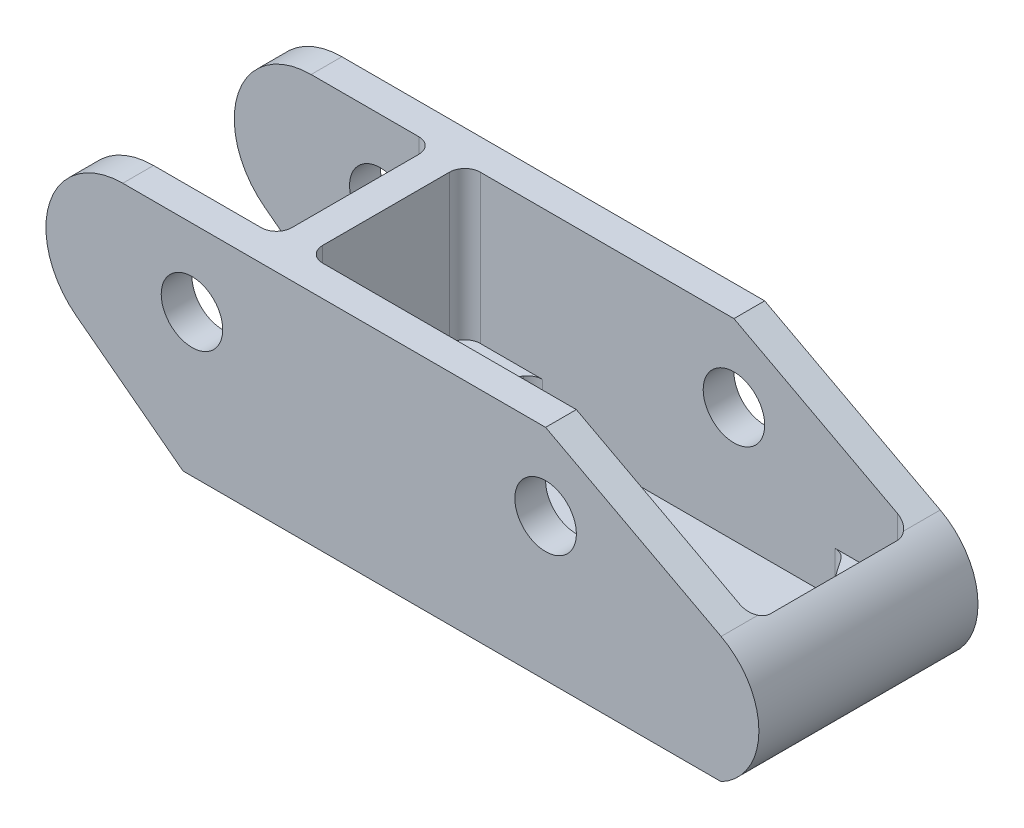
SolidWorks part; units mm, degrees
ref_plane "Front Plane" through (0, 0, 0) normal (0, 0, 1) x (1, 0, 0)
ref_plane "Top Plane" through (0, 0, 0) normal (0, 1, 0) x (1, 0, 0)
ref_plane "Right Plane" through (0, 0, 0) normal (1, 0, 0) x (0, 0, -1)
sketch "Sketch1" plane through (0, 0, 0) normal (0, 0, 1) x (1, 0, 0)
  line L0 (-35, 0) -> (35, 0)
  line L1 (-35, 0) -> (-48.879, 10.5347)
  line L2 (-42.833, 28.5) -> (12.167, 28.5)
  line L3 (12.167, 28.5) -> (35, 16.3595)
  line L4 (35, 0) -> (35, 45.6164) construction
  line L5 (12.167, 28.5) -> (12.167, -15.6419) construction
  arc A0 (-42.833, 28.5) -> (-48.879, 10.5347) centre (-42.833, 18.5) ccw
  arc A1 (35, 16.3595) -> (35, 0) centre (30.6508, 8.1797) cw
  circle A2 centre (12.167, 18.5) radius 4
  circle A4 centre (-33.833, 18.5) radius 4
  point P8 (0, 0)
  point P16 (0, 0)
  point P17 (0, 0)
  dimension "D4" = 10
  dimension "D8" = 8
  dimension "D1" = 142.8
  dimension "D2" = 28.5
  dimension "D3" = 70
  dimension "D5" = 55
  dimension "D6" = 152
  dimension "D7" = 10
  dimension "D9" = 46
extrude "Boss-Extrude1" add sketch "Sketch1" along normal mid plane 28.5
sketch "Sketch3" plane through (0, 28.5, 0) normal (0, 1, 0) x (1, 0, 0)
  line L0 (-52.833, 10.25) -> (-28.833, 10.25)
  line L1 (-52.833, 14.25) -> (-52.833, -14.25) construction
  line L2 (-26.833, 8.25) -> (-26.833, -8.25)
  line L3 (-28.833, -10.25) -> (-52.833, -10.25)
  line L4 (-52.833, -10.25) -> (-52.833, 10.25)
  line L5 (12.167, 14.25) -> (-42.833, 14.25) construction
  line L6 (12.167, -14.25) -> (-42.833, -14.25) construction
  line L7 (-20.833, 10.25) -> (33.4149, 10.25)
  line L8 (35.4149, 8.25) -> (35.4149, -8.25)
  line L9 (33.4149, -10.25) -> (-20.833, -10.25)
  line L10 (-22.833, -8.25) -> (-22.833, 8.25)
  line L11 (39.9149, -14.25) -> (39.9149, 14.25) construction
  arc A0 (35.4149, -8.25) -> (33.4149, -10.25) centre (33.4149, -8.25) cw
  arc A1 (33.4149, 10.25) -> (35.4149, 8.25) centre (33.4149, 8.25) cw
  arc A2 (-20.833, -10.25) -> (-22.833, -8.25) centre (-20.833, -8.25) cw
  arc A3 (-20.833, 10.25) -> (-22.833, 8.25) centre (-20.833, 8.25) ccw
  arc A4 (-26.833, -8.25) -> (-28.833, -10.25) centre (-28.833, -8.25) cw
  arc A5 (-28.833, 10.25) -> (-26.833, 8.25) centre (-28.833, 8.25) cw
  point P24 (-26.833, -10.25)
  point P27 (-26.833, 10.25)
  line M12 (-42.833, 14.25) -> (-42.833, -14.25)
  dimension "D5" = 2
  dimension "D1" = 4
  dimension "D2" = 4
  dimension "D3" = 26
  dimension "D4" = 4
  dimension "D6" = 4.5
extrude "Cut-Extrude1" cut sketch "Sketch3" against normal offset from surface (25 mm away) 3.5 contours A5 L0 L3 A4 L2 M12 | L4 L3 L0 M12 region at (-47.833, 28.5, 0) region at (-34.8727, 28.5, 0) up to face at (0, 0, 0)
extrude "Cut-Extrude2" cut sketch "Sketch3<3>" against normal blind 19.3 contours L9 A2 L10 A3 L7 A1 L8 A0
sketch "Sketch3<3>" plane through (0, 28.5, 0) normal (0, 1, 0) x (1, 0, 0) same geometry as "Sketch3"
sketch "Sketch6" plane through (0, 9.2, 0) normal (0, 1, 0) x (1, 0, 0)
  line L0 (-18.4833, 3.4067) -> (-14.3594, 9.3856)
  line L1 (-20.833, 10.25) -> (33.4149, 10.25) construction
  line L2 (-12.7131, 10.25) -> (25.295, 10.25)
  line L3 (26.9413, 9.3856) -> (31.0652, 3.4067)
  line L4 (31.0652, -3.4067) -> (26.9413, -9.3856)
  line L5 (33.4149, -10.25) -> (-20.833, -10.25) construction
  line L6 (25.295, -10.25) -> (-12.7131, -10.25)
  line L7 (-14.3594, -9.3856) -> (-18.4833, -3.4067)
  line L8 (-22.833, -8.25) -> (-22.833, 8.25) construction
  line L9 (35.4149, 8.25) -> (35.4149, -8.25) construction
  line L10 (35.4149, 8.25) -> (35.4149, -8.25) construction
  line L11 (-20.833, 10.25) -> (33.4149, 10.25) construction
  arc A0 (-12.7131, -10.25) -> (-14.3594, -9.3856) centre (-12.7131, -8.25) cw
  arc A1 (26.9413, -9.3856) -> (25.295, -10.25) centre (25.295, -8.25) cw
  arc A2 (25.295, 10.25) -> (26.9413, 9.3856) centre (25.295, 8.25) cw
  arc A3 (-14.3594, 9.3856) -> (-12.7131, 10.25) centre (-12.7131, 8.25) cw
  arc A4 (31.0652, 3.4067) -> (31.0652, -3.4067) centre (26.1261, 0) cw
  arc A5 (-18.4833, 3.4067) -> (-18.4833, -3.4067) centre (-13.5442, 0) ccw
  point P14 (6.291, 10.25)
  point P15 (6.291, -10.25)
  point P16 (0, 0)
  point P17 (0, 0)
  point P18 (0, 0)
  point P21 (-13.7632, -10.25)
  point P24 (26.3451, -10.25)
  point P27 (26.3451, 10.25)
  point P30 (-13.7632, 10.25)
  point P33 (33.4149, 0)
  point P36 (-20.833, 0)
  point P42 (-87.8655, 0)
  dimension "D3" = 2
  dimension "D4" = 6
  dimension "D7" = 38.008
  dimension "D1" = 2
  dimension "D2" = 2
  dimension "D5" = 2
  dimension "D6" = 2
extrude "Cut-Extrude3" cut sketch "Sketch6" against normal up to surface (5.7 mm away) up to face at (-31.6209, 3.5, 0)
sketch "Sketch7" plane through (0, 3.5, 0) normal (0, 1, 0) x (1, 0, 0)
  line L0 (39.9149, -14.25) -> (39.9149, 14.25) construction
  line L1 (-13.2851, 0) -> (48.6934, 0) construction
  line L2 (25.295, -10.25) -> (-12.7131, -10.25) construction
  circle A0 centre (26.7149, 0) radius 3
  circle A1 centre (-13.2851, 0) radius 3
  dimension "D3" = 6
  dimension "D1" = 13.2
  dimension "D2" = 40
  dimension "D4" = 10.25
extrude "Cut-Extrude4" cut sketch "Sketch7" against normal through all
